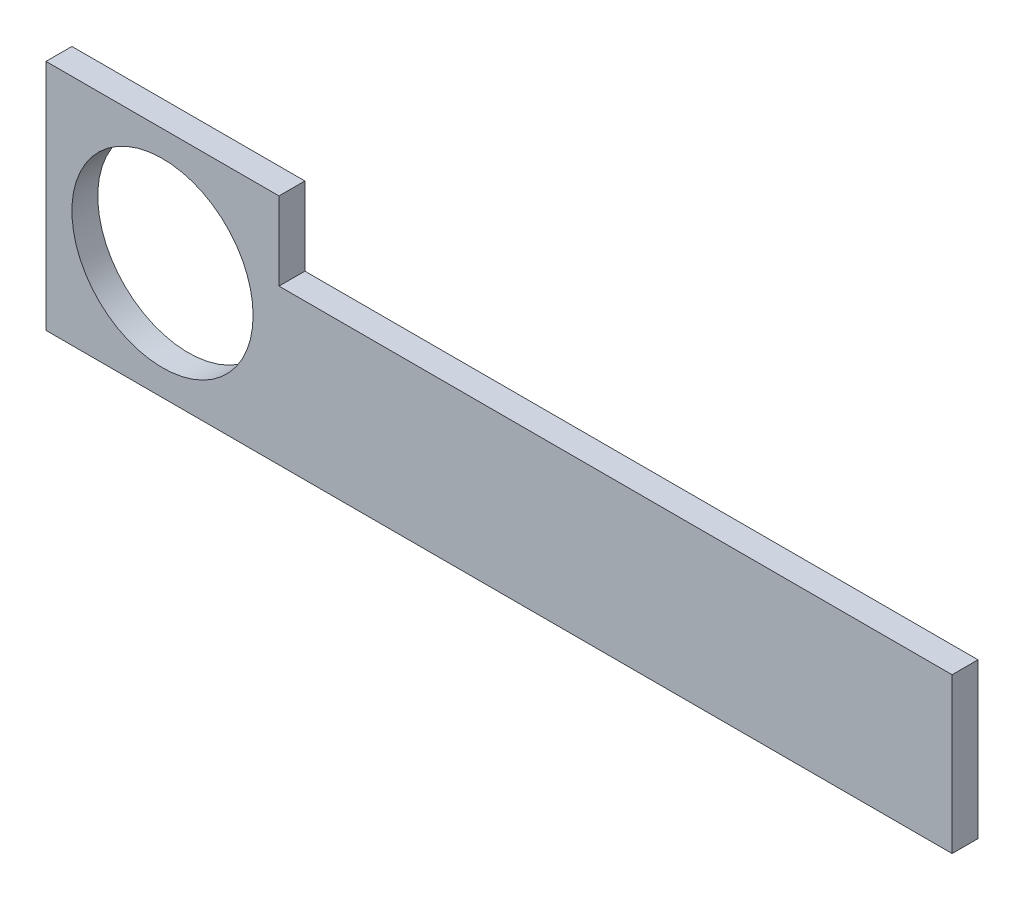
SolidWorks part; units mm, degrees
material "Plain Carbon Steel"
ref_plane "Front Plane" through (0, 0, 0) normal (0, 0, 1) x (1, 0, 0)
ref_plane "Top Plane" through (0, 0, 0) normal (0, 1, 0) x (1, 0, 0)
ref_plane "Right Plane" through (0, 0, 0) normal (1, 0, 0) x (0, 0, -1)
sketch "Sketch1" plane through (0, 0, 0) normal (0, 0, 1) x (1, 0, 0)
  line L0 (26.6994, -278.3313) -> (-267.3006, -278.3313) construction
  line L1 (-20.3006, -278.3313) -> (-280.3006, -278.3313)
  line L2 (-20.3006, -278.3313) -> (-20.3006, -338.1571)
  line L3 (-20.3006, -338.1571) -> (-370.3006, -338.1571)
  line L4 (-370.3006, -278.3313) -> (-370.3006, -338.1571)
  line L5 (-267.3006, -338.1571) -> (26.6994, -338.1571) construction
  line L6 (-20.3006, -285.3313) -> (-20.3006, -331.1571) construction
  line L8 (-280.3006, -278.3313) -> (-280.3006, -248.1571)
  line L9 (-280.3006, -248.1571) -> (-370.3006, -248.1571)
  line L10 (-370.3006, -248.1571) -> (-370.3006, -278.3313)
  line L11 (-270.3006, -285.3313) -> (-270.3006, -331.1571) construction
  line L12 (-280.3006, -248.1571) -> (-280.3006, -338.1571) construction
  line L13 (-370.3006, -293.1571) -> (-280.3006, -293.1571) construction
  line L14 (-325.3006, -248.1571) -> (-325.3006, -338.1571) construction
  line L15 (-325.3006, -293.1571) -> (-357.1204, -261.3373) construction
  line L16 (-325.3006, -293.1571) -> (-293.4808, -261.3373) construction
  line L17 (-325.3006, -293.1571) -> (-293.4808, -324.9769) construction
  line L18 (-325.3006, -293.1571) -> (-357.1204, -324.9769) construction
  circle A0 centre (-325.3006, -293.1571) radius 45 construction
  point P15 (-280.3006, -293.1571)
  point P21 (-325.3006, -293.1571)
  point P23 (-325.3006, -293.1571)
  point P32 (-325.3006, -293.1571)
  dimension "D1" = 90
  dimension "D2" = 10
  dimension "D3" = 90
  dimension "D5" = 45
  dimension "D6" = 4
extrude "Boss-Extrude1" add sketch "Sketch1" along normal blind 10
sketch "Sketch2" plane through (0, 0, 10) normal (0, 0, 1) x (1, 0, 0)
  circle A0 centre (-325.3006, -293.1571) radius 35
  dimension "D1" = 70
extrude "Cut-Extrude1" cut sketch "Sketch2" against normal through all
